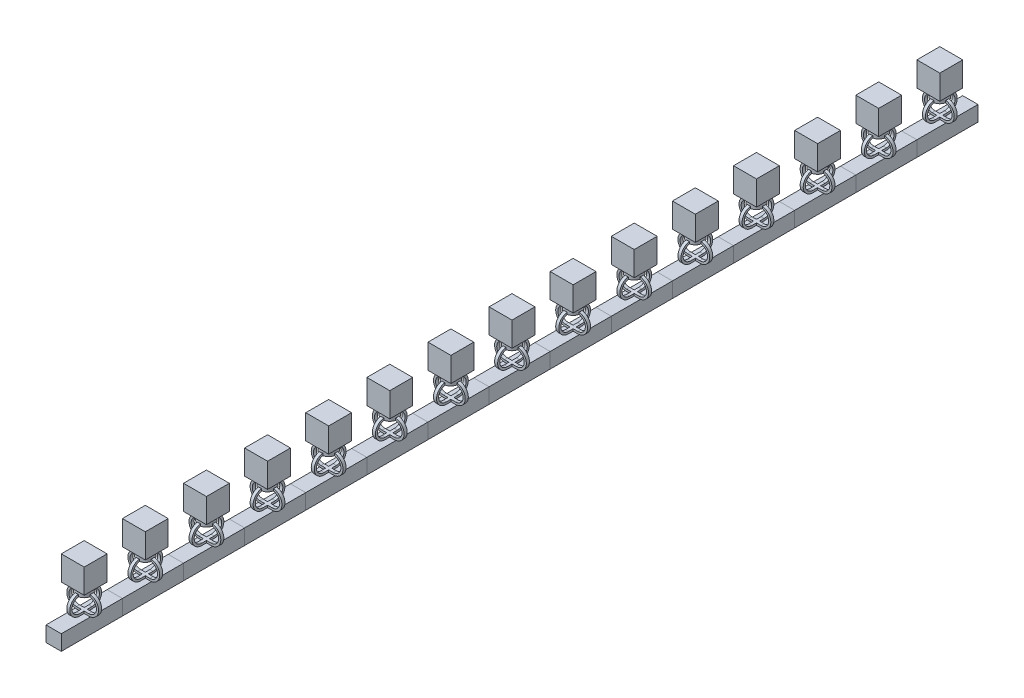
SolidWorks part; units mm, degrees
material "PLA"
ref_plane "Front Plane" through (0, 0, 0) normal (0, 0, 1) x (1, 0, 0)
ref_plane "Top Plane" through (0, 0, 0) normal (0, 1, 0) x (1, 0, 0)
ref_plane "Right Plane" through (0, 0, 0) normal (1, 0, 0) x (0, 0, -1)
sketch "Sketch1" plane through (0, 0, 0) normal (0, 0, 1) x (1, 0, 0)
  line L1 (-2.5, 2.5) -> (2.5, 2.5)
  line L2 (-2.5, 2.5) -> (-2.5, -2.5)
  line L3 (-2.5, -2.5) -> (2.5, -2.5)
  line L4 (2.5, 2.5) -> (2.5, -2.5)
  line L5 (-2.5, 2.5) -> (2.5, -2.5) construction
  line L6 (-2.5, -2.5) -> (2.5, 2.5) construction
  point P0 (0, 0)
  dimension "D1" = 5
  dimension "D2" = 5
extrude "Boss-Extrude1" add sketch "Sketch1" along normal mid plane 20
sketch "Sketch2" plane through (0, 0, 0) normal (0, 0, 1) x (1, 0, 0)
  line L0 (-2.5, 0) -> (2.5, 0) construction
  line L1 (-2.5, 2.5) -> (-2.5, -2.5) construction
  line L2 (2.5, -2.5) -> (2.5, 2.5) construction
  line L3 (0, 3.2) -> (-2, 3.2)
  line L4 (-2, 8.2) -> (0, 8.2)
  line L5 (0, 2.5) -> (-2, 2.5)
  line L6 (-2, 8.9) -> (0, 8.9)
  line L8 (0, 8.9) -> (0, 8.2)
  line L9 (2.5, 2.5) -> (-2.5, 2.5) construction
  line L10 (0, 3.2) -> (0, 2.5)
  arc A0 (-2, 3.2) -> (-2, 8.2) centre (-2, 5.7) cw
  arc A1 (-2, 2.5) -> (-2, 8.9) centre (-2, 5.7) cw
  dimension "D1" = 2.5
  dimension "t" = 0.7
  dimension "D2" = 2
extrude "Boss-Extrude2" add sketch "Sketch2" along normal mid plane 1
mirror "Mirror1" about plane through (0, 0, 0) normal (1, 0, 0) of "Boss-Extrude2"
sketch "Sketch3" plane through (0, 0, 0) normal (1, 0, 0) x (0, 0, -1)
  line L0 (0, 2.5) -> (-2, 2.5)
  line L2 (-10, 2.5) -> (10, 2.5) construction
  line L3 (-2, 8.9) -> (0, 8.9)
  line L4 (-0.5, 8.9) -> (0.5, 8.9) construction
  line L5 (0, 3.2) -> (-2, 3.2)
  line L6 (-2, 8.2) -> (0, 8.2)
  line L7 (0, 8.2) -> (0, 8.9)
  line L8 (0, 3.2) -> (0, 2.5)
  arc A0 (-2, 2.5) -> (-2, 8.9) centre (-2, 5.7) cw
  arc A1 (-2, 3.2) -> (-2, 8.2) centre (-2, 5.7) cw
  dimension "D2" = 3.2
  dimension "D3" = 2.5
  dimension "D1" = 2
extrude "Boss-Extrude3" add sketch "Sketch3" along normal mid plane 1
mirror "Mirror2" about plane through (0, 0, 0) normal (0, 0, 1) of "Boss-Extrude3"
sketch "Sketch4" plane through (0, 8.9, 0) normal (0, 1, 0) x (1, 0, 0)
  line L1 (-3.75, 3.75) -> (3.75, 3.75)
  line L2 (-3.75, 3.75) -> (-3.75, -3.75)
  line L3 (-3.75, -3.75) -> (3.75, -3.75)
  line L4 (3.75, 3.75) -> (3.75, -3.75)
  line L5 (-3.75, 3.75) -> (3.75, -3.75) construction
  line L6 (-3.75, -3.75) -> (3.75, 3.75) construction
  point P0 (0, 0)
  dimension "D1" = 7.5
  dimension "D2" = 7.5
extrude "Boss-Extrude4" add sketch "Sketch4" along normal blind 10 separate body
chamfer "Chamfer1" distance 2 angle 45 4 edges at (3.75, 8.9, 0) (0, 8.9, 3.75) (-3.75, 8.9, 0) (0, 8.9, -3.75)
sketch "Sketch5" plane through (0, 8.2, 0) normal (0, -1, 0) x (1, 0, 0)
  circle A0 centre (0, 0) radius 2.4749
extrude "Boss-Extrude5" add sketch "Sketch5" against normal up to next
pattern_linear "LPattern2" count 15 spacing 20 along (0, 0, 1) of bodies 108
equation "\"a\"= 5mm'Dimenzija nosilca"
equation "\"w\"= 1mm'Širina vzmeti"
equation "\"t\"= 0.7mm'Debelina vzmeti"
equation "\"r\"= 2.5mm'Polmer loka vmzeti"
equation "\"rr\"= 10mm'Polmer resonatorja"
equation "\"L\"= 20mm'Dolžina bazne celice"
equation "\"t@Sketch2\"=\"t\""
equation "\"D1@Sketch2\"=\"r\""
equation "\"D1@Sketch1\"=\"a\""
equation "\"D2@Sketch1\"=\"a\""
equation "\"D1@Boss-Extrude1\"=\"L\""
equation "\"D2@Sketch3\"=\"r\"+\"t\""
equation "\"D3@Sketch3\"=\"r\""
equation "\"D1@Boss-Extrude3\"=\"w\""
equation "\"N\"= 15'Amount of cells"
equation "\"D3@LPattern2\"=\"L\""
equation "\"D1@LPattern2\"=\"N\""
equation "\"D1@Boss-Extrude2\"=\"w\""
